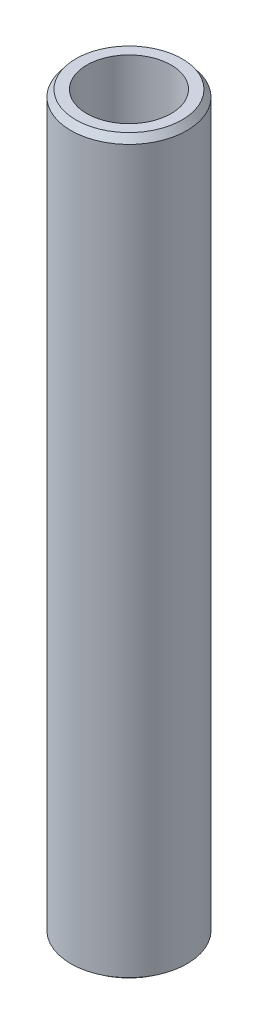
SolidWorks part; units mm, degrees
ref_plane "Front Plane" through (0, 0, 0) normal (0, 0, 1) x (1, 0, 0)
ref_plane "Top Plane" through (0, 0, 0) normal (0, 1, 0) x (1, 0, 0)
ref_plane "Right Plane" through (0, 0, 0) normal (1, 0, 0) x (0, 0, -1)
sketch "Sketch1" plane through (0, 0, 0) normal (0, 1, 0) x (1, 0, 0)
  circle A0 centre (0, 0) radius 47.5
  dimension "SHAFT_OD" = 95
extrude "Boss-Extrude1" add sketch "Sketch1" along normal blind 600
sketch "Sketch2" plane through (0, 0, 0) normal (0, 1, 0) x (1, 0, 0)
  circle A0 centre (0, 0) radius 34.4798
  dimension "BORE_D" = 68.9596
extrude "Cut-Extrude1" cut sketch "Sketch2" along normal through all
chamfer "Chamfer1" distance 5.4783 angle 36.811 2 edges at (0, 600, 47.5) (0, 0, 47.5) first distance on face at (0, 600, 47.5) first distance on face at (0, 0, 34.4798)
